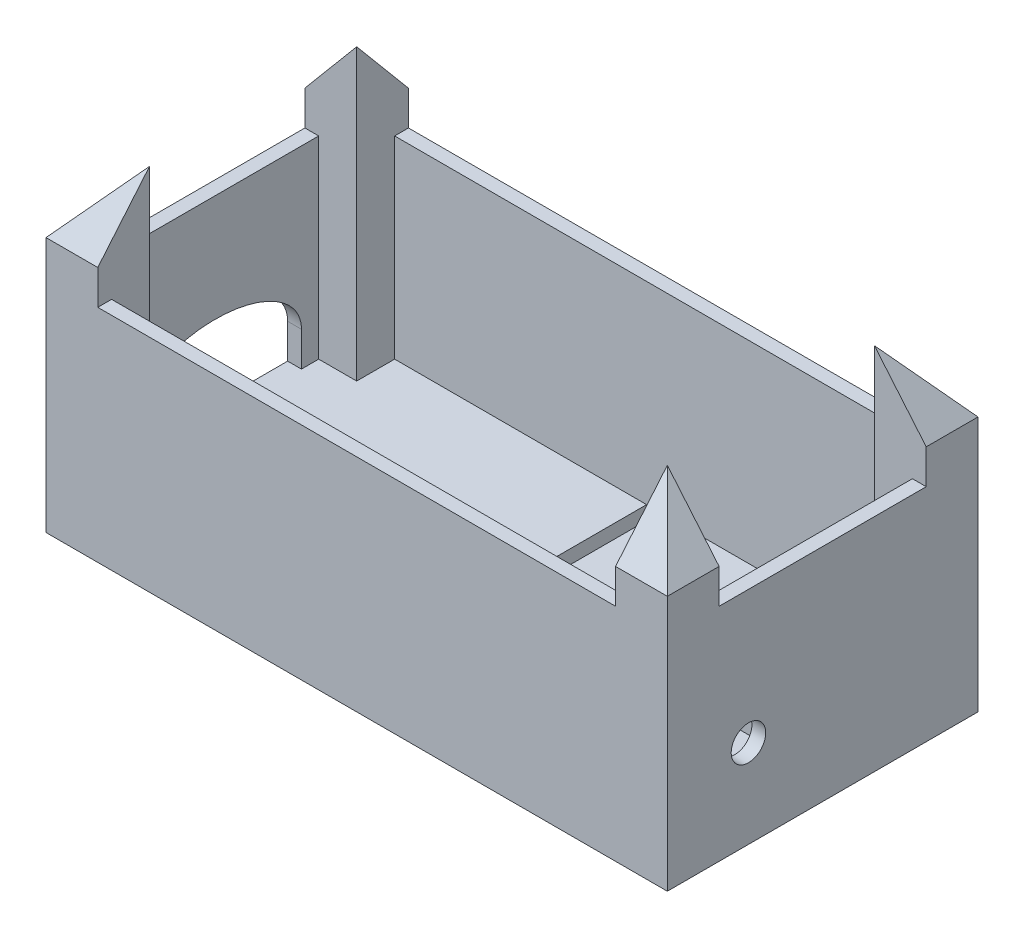
SolidWorks part; units mm, degrees
ref_plane "Front Plane" through (0, 0, 0) normal (0, 0, 1) x (1, 0, 0)
ref_plane "Top Plane" through (0, 0, 0) normal (0, 1, 0) x (1, 0, 0)
ref_plane "Right Plane" through (0, 0, 0) normal (1, 0, 0) x (0, 0, -1)
sketch "Sketch1" plane through (0, 0, 0) normal (0, 1, 0) x (1, 0, 0)
  line L1 (0, 0) -> (180, 0)
  line L2 (0, 0) -> (0, -90)
  line L3 (0, -90) -> (180, -90)
  line L4 (180, 0) -> (180, -90)
  dimension "D1" = 180
  dimension "D2" = 90
extrude "Boss-Extrude1" add sketch "Sketch1" along normal blind 64
shell "Shell1" thickness 4 removed face at (90, 64, 45)
sketch "Sketch2" plane through (180, 0, 0) normal (1, 0, 0) x (0, 0, -1)
  line L1 (-90, 64) -> (-90, 0) construction
  line L2 (-90, 0) -> (0, 0) construction
  circle A0 centre (-66.5, 25.5) radius 5
  dimension "D1" = 10
  dimension "D2" = 25.5
  dimension "D3" = 23.5
extrude "Cut-Extrude1" cut sketch "Sketch2" against normal up to surface (4 mm away) up to face at (176, 34, 45)
sketch "Sketch4" plane through (0, 4, 0) normal (0, 1, 0) x (1, 0, 0)
  line L0 (176, -45) -> (4, -45) construction
  line L1 (176, -86) -> (176, -4) construction
  line L2 (4, -4) -> (4, -86) construction
  line L3 (90, -86) -> (90, -4) construction
  line L4 (4, -86) -> (176, -86) construction
  line L5 (176, -4) -> (4, -4) construction
  circle A0 centre (90, -45) radius 2
  dimension "D1" = 4
extrude "Cut-Extrude2" cut sketch "Sketch4" against normal through all
sketch "Sketch7" plane through (0, 4, 0) normal (0, 1, 0) x (1, 0, 0)
  line L1 (0, 0) -> (15, 0)
  line L2 (0, 0) -> (0, -15)
  line L3 (0, -15) -> (15, -15)
  line L4 (15, 0) -> (15, -15)
  line L5 (180, 0) -> (165, 0)
  line L6 (180, 0) -> (180, -15)
  line L7 (180, -15) -> (165, -15)
  line L8 (165, 0) -> (165, -15)
  line L9 (180, -90) -> (165, -90)
  line L10 (180, -90) -> (180, -75)
  line L11 (180, -75) -> (165, -75)
  line L12 (165, -90) -> (165, -75)
  line L13 (0, -90) -> (15, -90)
  line L14 (0, -90) -> (0, -75)
  line L15 (0, -75) -> (15, -75)
  line L16 (15, -90) -> (15, -75)
  dimension "D1" = 15
  dimension "D2" = 15
  dimension "D3" = 15
  dimension "D4" = 15
  dimension "D5" = 15
  dimension "D6" = 15
  dimension "D7" = 15
  dimension "D8" = 15
extrude "Boss-Extrude3" add sketch "Sketch7" along normal blind 90
sketch "Sketch8" plane through (0, 0, 90) normal (0, 0, 1) x (1, 0, 0)
  line L0 (0, 74) -> (90, 181.2578)
  line L1 (90, 181.2578) -> (180, 74)
  line L2 (180, 74) -> (180, 221.1504)
  line L3 (180, 221.1504) -> (-17.5941, 221.1504)
  line L4 (-17.5941, 221.1504) -> (-17.5941, 74)
  line L5 (-17.5941, 74) -> (0, 74)
  line L6 (0, 94) -> (0, 0) construction
  line L7 (180, 94) -> (180, 0) construction
  line L8 (165, 94) -> (180, 94) construction
  line L9 (0, 94) -> (15, 94) construction
  point P12 (172.5, 94)
  point P13 (-8.797, 74)
  dimension "D1" = 40
  dimension "D2" = 40
  dimension "D3" = 0
  dimension "D4" = 0
  dimension "D5" = 20
  dimension "D6" = 20
  dimension "D7" = 147.1504
  dimension "D8" = 17.5941
extrude "Cut-Extrude4" cut sketch "Sketch8" against normal through all
sketch "Sketch10" plane through (180, 0, 0) normal (1, 0, 0) x (0, 0, -1)
  line L0 (-90, 74) -> (-45, 127.6289)
  line L1 (-45, 127.6289) -> (0, 74)
  line L2 (0, 74) -> (0, 140.5126)
  line L3 (0, 140.5126) -> (-124.3013, 140.5126)
  line L4 (-124.3013, 140.5126) -> (-124.3013, 74)
  line L5 (-124.3013, 74) -> (-90, 74)
  line L6 (-90, 91.8763) -> (-90, 74) construction
  line L7 (0, 91.8763) -> (0, 74) construction
  line L8 (-75, 64) -> (-15, 64) construction
  dimension "D1" = 40
  dimension "D2" = 40
  dimension "D3" = 0
  dimension "D4" = 90
  dimension "D5" = 0
  dimension "D6" = 12.8837
  dimension "D7" = 34.3013
extrude "Cut-Extrude5" cut sketch "Sketch10" against normal through all
hole_wizard "M3x0.5 Tapped Hole1" positions "Sketch12" profile "Sketch13" tap size "M3x0.5" standard "ANSI Metric"
sketch "Sketch12" plane through (0, 0, 0) normal (0, -1, 0) x (-1, 0, 0)
  line L0 (-180, 0) -> (0, 0) construction
  line L1 (-180, -90) -> (-180, 0) construction
  line L2 (0, 0) -> (0, -90) construction
  line L3 (0, -90) -> (-180, -90) construction
  point P0 (-172.5, -7.5)
  point P2 (-7.5, -7.5)
  point P4 (-7.5, -82.5)
  point P6 (-172.5, -82.5)
  dimension "D1" = 7.5
  dimension "D2" = 7.5
  dimension "D3" = 7.5
  dimension "D4" = 7.5
  dimension "D5" = 7.5
  dimension "D6" = 7.5
  dimension "D7" = 7.5
  dimension "D8" = 7.5
sketch "Sketch13" plane through (172.5, 0, 7.5) normal (1, 0, 0) x (0, 0, -1)
  line L0 (0, 0) -> (0, 8.2511)
  line L1 (0, 8.2511) -> (1.25, 7.5)
  line L2 (1.25, 7.5) -> (1.25, 0)
  line L5 (1.25, 0) -> (0, 0)
  line L10 (0, 8.2511) -> (-1.25, 7.5) construction
  line L11 (0, -6.35) -> (0, 107.95) construction
  dimension "Tap Drill Dia." = 2.5
  dimension "Tap Drill Depth" = 7.5
  dimension "Drill Angle" = 118
sketch "Sketch17" plane through (0, 4, 0) normal (0, 1, 0) x (1, 0, 0)
  line L0 (165, -4) -> (15, -4) construction
  line L1 (4, -4) -> (88, -4)
  line L2 (4, -4) -> (4, -43)
  line L3 (4, -43) -> (88, -43)
  line L4 (88, -4) -> (88, -43)
  line L5 (4, -15) -> (4, -75) construction
  line L6 (176, -45) -> (4, -45) construction
  line L7 (176, -75) -> (176, -15) construction
  line L8 (90, -4) -> (90, -86) construction
  line L9 (15, -86) -> (165, -86) construction
  line L10 (176, -4) -> (92, -4)
  line L11 (176, -4) -> (176, -43)
  line L12 (176, -43) -> (92, -43)
  line L13 (92, -4) -> (92, -43)
  line L14 (176, -86) -> (176, -47)
  line L15 (176, -47) -> (92, -47)
  line L16 (176, -86) -> (92, -86)
  line L17 (92, -86) -> (92, -47)
  line L18 (4, -86) -> (4, -47)
  line L19 (4, -86) -> (88, -86)
  line L20 (88, -86) -> (88, -47)
  line L21 (4, -47) -> (88, -47)
  circle A0 centre (90, -45) radius 2 construction
  dimension "D1" = 0
  dimension "D2" = 0
  dimension "D3" = 2
  dimension "D4" = 2
extrude "Boss-Extrude5" add sketch "Sketch17" along normal blind 4
sketch "Sketch15" plane through (0, 0, 0) normal (-1, 0, 0) x (0, 0, 1)
  line L0 (15, 8) -> (43, 8) construction
  line L1 (45, 33) -> (45, 40.2823) construction
  line L3 (0, 74) -> (0, 0) construction
  line L5 (20, 18) -> (20, 8)
  line L6 (20, 8) -> (70, 8)
  line L7 (70, 18) -> (70, 8)
  line L8 (90, 74) -> (90, 0) construction
  ellipse E0 centre (45, 18) end of major axis (70, 18) minor radius 15 (70, 18) -> (20, 18) ccw
  dimension "D1" = 10
  dimension "D2" = 20
  dimension "D3" = 20
  dimension "D4" = 0
  dimension "D5" = 10
  dimension "D6" = 25
  dimension "D7" = 30
extrude "Cut-Extrude6" cut sketch "Sketch15" against normal up to surface (4 mm away) up to face at (4, 21, 45)
sketch "Sketch18" plane through (0, 0, 0) normal (-1, 0, 0) x (0, 0, 1)
  line L0 (10.9, 7.75) -> (79.1, 7.75) construction
  line L1 (45, 8) -> (45, 47.0126) construction
  line L2 (20, 8) -> (70, 8) construction
  line L3 (20, 18) -> (20, 8) construction
  line L4 (70, 8) -> (70, 18) construction
  circle A0 centre (77.75, 7.75) radius 1.5
  circle A2 centre (45, 42.25) radius 1.5
  circle A3 centre (12.25, 7.75) radius 1.5
  point P12 (45, 7.75)
  dimension "D1" = 3
  dimension "D3" = 34.25
  dimension "D6" = 7.75
  dimension "D7" = 0.25
  dimension "D8" = 3
  dimension "D9" = 3
  dimension "D2" = 0.25
  dimension "D4" = 9.1
  dimension "D5" = 7.75
extrude "Cut-Extrude7" cut sketch "Sketch18" against normal blind 2
